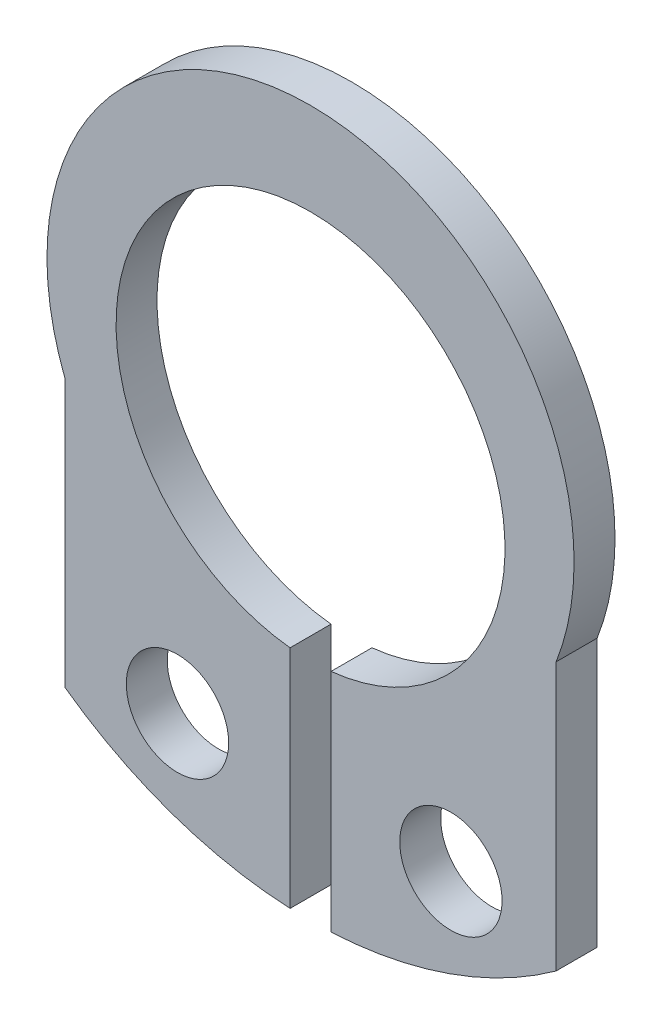
SolidWorks part; units mm, degrees
ref_plane "Plan de face" through (0, 0, 0) normal (0, 0, 1) x (1, 0, 0)
ref_plane "Plan de dessus" through (0, 0, 0) normal (0, 1, 0) x (1, 0, 0)
ref_plane "Plan de droite" through (0, 0, 0) normal (1, 0, 0) x (0, 0, -1)
ref_plane "Plan1" through (0, 0, 0) normal (0, 0, -1) x (-1, 0, 0)
sketch "Esquisse1" plane through (0, 0, 0) normal (0, 0, -1) x (-1, 0, 0)
  line L0 (0.0927, 0.3079) -> (0.0927, -1.8977)
  line L1 (2.2927, -1.1268) -> (2.2927, 1.4893)
  line L2 (-2.5073, 1.4893) -> (-2.5073, -1.1268)
  line L3 (-0.3073, -1.8977) -> (-0.3073, 0.3079)
  arc A0 (-0.3073, 0.3079) -> (0.0927, 0.3079) centre (-0.1073, 2.1974) cw
  arc A1 (0.0927, -1.8977) -> (2.2927, -1.1268) centre (-0.1073, 2.1974) ccw
  arc A2 (2.2927, 1.4893) -> (-2.5073, 1.4893) centre (-0.1073, 2.4224) ccw
  arc A3 (-2.5073, -1.1268) -> (-0.3073, -1.8977) centre (-0.1073, 2.1974) ccw
  circle A4 centre (1.1927, -0.7977) radius 0.5
  circle A5 centre (-1.4787, -0.7977) radius 0.5
extrude "Boss.-Extru.1" add sketch "Esquisse1" against normal blind 0.4
